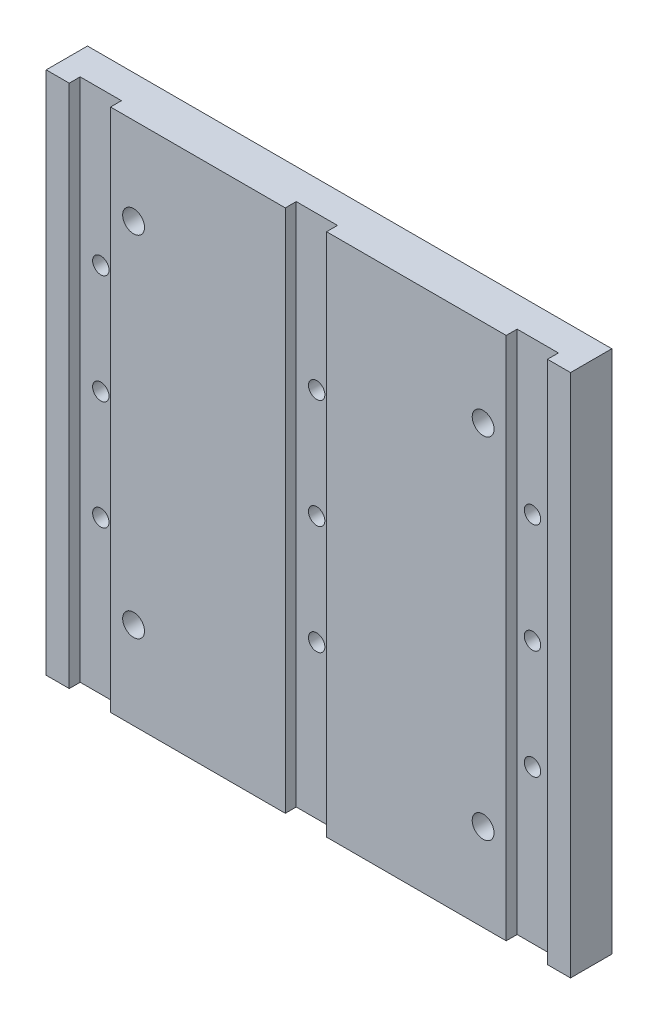
SolidWorks part; units mm, degrees
material "Acrylic (Medium-high impact)"
ref_plane "Front Plane" through (0, 0, 0) normal (0, 0, 1) x (1, 0, 0)
ref_plane "Top Plane" through (0, 0, 0) normal (0, 1, 0) x (1, 0, 0)
ref_plane "Right Plane" through (0, 0, 0) normal (1, 0, 0) x (0, 0, -1)
sketch "Sketch1" plane through (0, 0, 0) normal (0, 0, 1) x (1, 0, 0)
  line L1 (-76.2, 76.2) -> (76.2, 76.2)
  line L2 (-76.2, 76.2) -> (-76.2, -76.2)
  line L3 (-76.2, -76.2) -> (76.2, -76.2)
  line L4 (76.2, 76.2) -> (76.2, -76.2)
  line L5 (-76.2, 76.2) -> (76.2, -76.2) construction
  line L6 (-76.2, -76.2) -> (76.2, 76.2) construction
  circle A0 centre (-50.8, 50.8) radius 3.175
  circle A1 centre (50.8, 50.8) radius 3.175
  circle A2 centre (50.8, -50.8) radius 3.175
  circle A3 centre (-50.8, -50.8) radius 3.175
  point P0 (0, 0)
  dimension "D9" = 6.35
  dimension "D10" = 6.35
  dimension "D13" = 6.35
  dimension "D14" = 6.35
  dimension "D1" = 0
  dimension "D2" = 0
  dimension "D3" = 152.4
  dimension "D4" = 152.4
  dimension "D5" = 25.4
  dimension "D6" = 25.4
  dimension "D7" = 25.4
  dimension "D8" = 25.4
  dimension "D11" = 25.4
  dimension "D12" = 25.4
  dimension "D15" = 25.4
  dimension "D16" = 25.4
extrude "Boss-Extrude1" add sketch "Sketch1" along normal blind 12
sketch "Sketch2" plane through (0, 0, 12) normal (0, 0, 1) x (1, 0, 0)
  line L0 (-76.2, -76.2) -> (76.2, -76.2) construction
  line L1 (-69.5, 76.2) -> (-57.5, 76.2)
  line L2 (-69.5, 76.2) -> (-69.5, -76.2)
  line L3 (-69.5, -76.2) -> (-57.5, -76.2)
  line L4 (-57.5, 76.2) -> (-57.5, -76.2)
  line L5 (-69.5, 76.2) -> (-57.5, -76.2) construction
  line L6 (-69.5, -76.2) -> (-57.5, 76.2) construction
  line L7 (-6.7, 76.2) -> (5.3, 76.2)
  line L8 (-6.7, 76.2) -> (-6.7, -76.2)
  line L9 (-6.7, -76.2) -> (5.3, -76.2)
  line L10 (5.3, 76.2) -> (5.3, -76.2)
  line L11 (-6.7, 76.2) -> (5.3, -76.2) construction
  line L12 (-6.7, -76.2) -> (5.3, 76.2) construction
  line L13 (57.5, 76.2) -> (69.5, 76.2)
  line L14 (57.5, 76.2) -> (57.5, -76.2)
  line L15 (57.5, -76.2) -> (69.5, -76.2)
  line L16 (69.5, 76.2) -> (69.5, -76.2)
  line L17 (57.5, 76.2) -> (69.5, -76.2) construction
  line L18 (57.5, -76.2) -> (69.5, 76.2) construction
  line L19 (-76.2, 76.2) -> (-76.2, -76.2) construction
  line L20 (76.2, -76.2) -> (76.2, 76.2) construction
  point P0 (-63.5, 0)
  point P5 (-0.7, 0)
  point P10 (63.5, 0)
  dimension "D1" = 12
  dimension "D2" = 0
  dimension "D3" = 152.4
  dimension "D4" = 12.7
  dimension "D5" = 0
  dimension "D6" = 12
  dimension "D7" = 152.4
  dimension "D8" = 50.8
  dimension "D9" = 0
  dimension "D10" = 12
  dimension "D11" = 152.4
  dimension "D12" = 12.7
extrude "Cut-Extrude1" cut sketch "Sketch2" against normal blind 3.175
sketch "Sketch3" plane through (0, 0, 8.825) normal (0, 0, 1) x (1, 0, 0)
  line L0 (-63.5, 0) -> (-63.5, 31.75) construction
  line L1 (-63.5, 0) -> (-63.5, -31.75) construction
  line L2 (-69.5, 0) -> (-57.5, 0) construction
  line L3 (-69.5, 76.2) -> (-69.5, -76.2) construction
  line L4 (-57.5, -76.2) -> (-57.5, 76.2) construction
  line L5 (-67.4717, 76.2) -> (-67.4717, -76.2) construction
  line L6 (-57.5, 76.2) -> (-69.5, 76.2) construction
  line L7 (-69.5, -76.2) -> (-57.5, -76.2) construction
  circle A0 centre (-63.5, 0) radius 2.3812
  circle A1 centre (-63.5, 31.75) radius 2.3812
  circle A2 centre (-63.5, -31.75) radius 2.3812
  point P14 (-67.4717, 0)
  point P16 (-63.5, 0)
  dimension "D2" = 4.7625
  dimension "D1" = 31.75
extrude "Cut-Extrude2" cut sketch "Sketch3" against normal through all
sketch "Sketch4" plane through (0, 0, 0) normal (0, 0, -1) x (-1, 0, 0)
  circle A0 centre (63.5, 31.75) radius 3.9687
  circle A1 centre (63.5, 0) radius 3.9687
  circle A2 centre (63.5, -31.75) radius 3.9687
  dimension "D1" = 7.9375
extrude "Cut-Extrude3" cut sketch "Sketch4" against normal blind 5.08
pattern_linear "LPattern1" count 3 spacing 62.738 along (1, 0, 0) of "Cut-Extrude2", "Cut-Extrude3"
